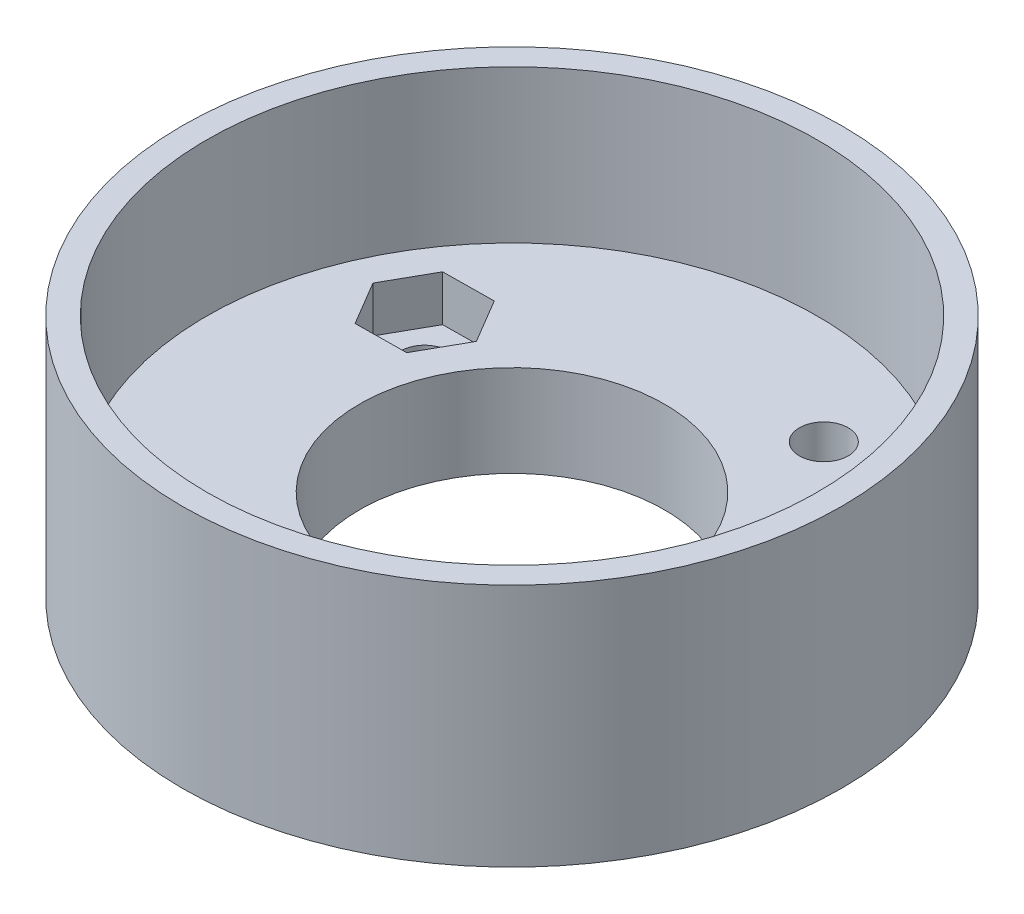
SolidWorks part; units mm, degrees
ref_plane "Front Plane" through (0, 0, 0) normal (0, 0, 1) x (1, 0, 0)
ref_plane "Top Plane" through (0, 0, 0) normal (0, 1, 0) x (1, 0, 0)
ref_plane "Right Plane" through (0, 0, 0) normal (1, 0, 0) x (0, 0, -1)
sketch "Sketch1" plane through (0, 0, 0) normal (0, 1, 0) x (1, 0, 0)
  line L0 (4.902, 8.7161) -> (9.8041, 17.4321) construction
  line L2 (10.234, 14.781) -> (7.3153, 16.4225)
  line L3 (7.3153, 16.4225) -> (4.4344, 14.7156)
  line L4 (4.4344, 14.7156) -> (4.4721, 11.3672)
  line L5 (4.4721, 11.3672) -> (7.3908, 9.7257)
  line L6 (7.3908, 9.7257) -> (10.2718, 11.4326)
  line L7 (10.2718, 11.4326) -> (10.234, 14.781)
  circle A0 centre (0, 0) radius 20
  circle A1 centre (0, 0) radius 10
  circle A2 centre (0, 0) radius 21.6
  circle A3 centre (7.3531, 13.0741) radius 1.6
  circle A6 centre (7.3531, 13.0741) radius 2.9 construction
  dimension "D1" = 40
  dimension "D4" = 3.2
  dimension "D2" = 10
  dimension "D3" = 1.6
  dimension "D5" = 5.8
extrude "Boss-Extrude1" add sketch "Sketch1" along normal blind 10 contours A2 A0 region at (-20.9891, 0, 0)
extrude "Boss-Extrude2" add sketch "Sketch1<3>" against normal blind 6 contours A2 A0 | A0 A1 L7 L6 L5 L4 L3 L2 | L6 L7 L2 L3 L4 L5 A3 | A3 region at (10.1641, 0, -13.1058) region at (-19.4343, 0, 0) region at (-20.9891, 0, 0) region at (7.3531, 0, -13.0741)
sketch "Sketch1<3>" plane through (0, 0, 0) normal (0, 1, 0) x (1, 0, 0) same geometry as "Sketch1"
extrude "Cut-Extrude2" cut sketch "Sketch1<5>" against normal through all contours A3 region at (7.3531, 0, -13.0741)
sketch "Sketch1<5>" plane through (0, 0, 0) normal (0, 1, 0) x (1, 0, 0) same geometry as "Sketch1"
extrude "Cut-Extrude1" cut sketch "Sketch1<4>" along normal blind 3 from surface contours L7 L2 L3 L4 L5 L6 starting at face at (7.3531, -6, -11.4741)
sketch "Sketch1<4>" plane through (0, 0, 0) normal (0, 1, 0) x (1, 0, 0) same geometry as "Sketch1"
extrude "Boss-Extrude3" add sketch "Sketch1<6>" along normal blind 0.2 from surface contours A3 region at (7.3531, 0, -13.0741) starting at face at (7.3531, -3, -13.0741)
sketch "Sketch1<6>" plane through (0, 0, 0) normal (0, 1, 0) x (1, 0, 0) same geometry as "Sketch1"
pattern_circular "CirPattern2" count 2 every 180 about axis through (0, 0, 0) along (0, 1, 0) of "Cut-Extrude2", "Boss-Extrude3", "Cut-Extrude1"
sketch "Sketch3" plane through (0, 0, 0) normal (0, 1, 0) x (1, 0, 0)
  line L0 (-7.3531, -13.0741) -> (7.3531, 13.0741) construction
  line L1 (8.7161, -4.902) -> (17.4321, -9.8041) construction
  line L2 (-7.3531, -13.0741) -> (13.0741, -7.3531) construction
  line L3 (13.0741, -7.3531) -> (7.3531, 13.0741) construction
  line L5 (9.7257, -7.3908) -> (11.4326, -10.2718)
  line L6 (11.4326, -10.2718) -> (14.781, -10.234)
  line L7 (14.781, -10.234) -> (16.4225, -7.3153)
  line L8 (16.4225, -7.3153) -> (14.7156, -4.4344)
  line L9 (14.7156, -4.4344) -> (11.3672, -4.4721)
  line L10 (11.3672, -4.4721) -> (9.7257, -7.3908)
  circle A0 centre (0, 0) radius 10 construction
  circle A1 centre (0, 0) radius 20 construction
  circle A2 centre (7.3531, 13.0741) radius 1.6 construction
  circle A3 centre (-7.3531, -13.0741) radius 1.6 construction
  circle A4 centre (0, 0) radius 10
  circle A5 centre (0, 0) radius 20
  circle A6 centre (7.3531, 13.0741) radius 1.6
  circle A7 centre (-7.3531, -13.0741) radius 1.6
  circle A8 centre (13.0741, -7.3531) radius 1.6
  circle A9 centre (13.0741, -7.3531) radius 2.9 construction
  dimension "D1" = 3.2
  dimension "D2" = 5.8
extrude "Cut-Extrude4" cut sketch "Sketch3" against normal through all contours A8 region at (13.0741, 0, 7.3531)
extrude "Cut-Extrude5" cut sketch "Sketch3<3>" against normal blind 3 contours L9 L10 L5 L6 L7 L8 A8 region at (10.6239, 0, 5.975)
sketch "Sketch3<3>" plane through (0, 0, 0) normal (0, 1, 0) x (1, 0, 0) same geometry as "Sketch3"
pattern_circular "CirPattern3" count 2 every 180 about axis through (0, 0, 0) along (0, 1, 0) of "Cut-Extrude4", "Cut-Extrude5"
equation "\"M3Bolt\"=3.2"
equation "\"D4@Sketch1\"=\"M3Bolt\""
equation "\"M3Nut\"=5.8"
equation "\"D5@Sketch1\"=\"M3Nut\""
equation "\"D1@Sketch3\"=\"M3Bolt\""
equation "\"D2@Sketch3\"=\"M3Nut\""
